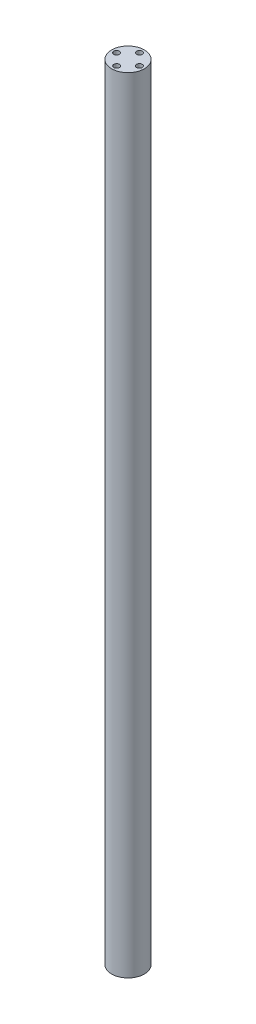
SolidWorks part; units mm, degrees
ref_plane "Front Plane" through (0, 0, 0) normal (0, 0, 1) x (1, 0, 0)
ref_plane "Top Plane" through (0, 0, 0) normal (0, 1, 0) x (1, 0, 0)
ref_plane "Right Plane" through (0, 0, 0) normal (1, 0, 0) x (0, 0, -1)
sketch "Sketch1" plane through (0, 0, 0) normal (0, 1, 0) x (1, 0, 0)
  circle A0 centre (0, 0) radius 12.7
  dimension "D1" = 25.4
extrude "Boss-Extrude1" add sketch "Sketch1" along normal blind 609.6 contours A0
sketch "Sketch2" plane through (0, 0, 0) normal (0, -1, 0) x (1, 0, 0)
  circle A0 centre (0, 0) radius 3.9688
  dimension "D1" = 7.9375
extrude "Cut-Extrude1" cut sketch "Sketch2" against normal blind 76.2 contours A0
sketch "Sketch3" plane through (0, 609.6, 0) normal (0, 1, 0) x (1, 0, 0)
  circle A0 centre (0, 0) radius 8.89 construction
  circle A1 centre (0, 8.89) radius 2.1971
  circle A2 centre (8.89, 0) radius 2.1971
  circle A3 centre (0, -8.89) radius 2.1971
  circle A4 centre (-8.89, 0) radius 2.1971
  dimension "D1" = 17.78
  dimension "D2" = 4.3942
  dimension "D3" = 4
extrude "Cut-Extrude2" cut sketch "Sketch3" against normal blind 76.2 contours A2 | A3 | A4 | A1
